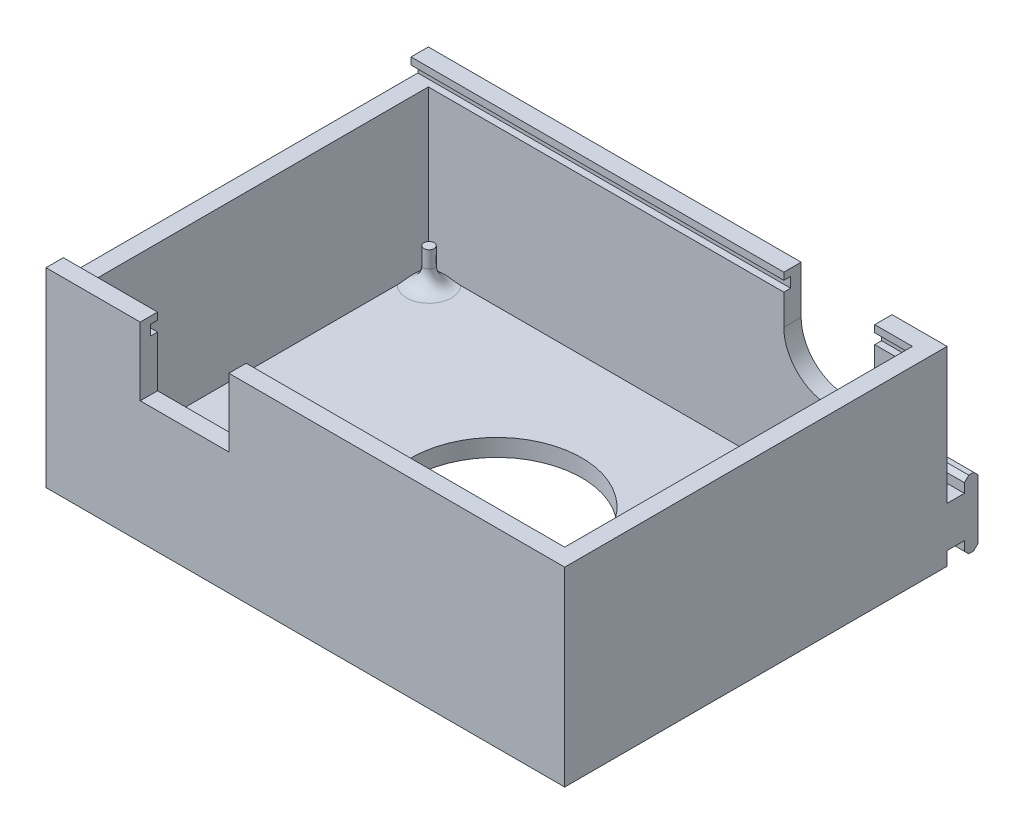
SolidWorks part; units mm, degrees
ref_plane "Front Plane" through (0, 0, 0) normal (0, 0, 1) x (1, 0, 0)
ref_plane "Top Plane" through (0, 0, 0) normal (0, 1, 0) x (1, 0, 0)
ref_plane "Right Plane" through (0, 0, 0) normal (1, 0, 0) x (0, 0, -1)
sketch "Sketch1" plane through (0, 0, 0) normal (0, 1, 0) x (1, 0, 0)
  line L0 (2.54, 2.54) -> (73.54, 2.54)
  line L1 (0, 0) -> (76.08, 0)
  line L2 (0, 0) -> (0, 56.08)
  line L3 (0, 56.08) -> (76.08, 56.08)
  line L4 (76.08, 0) -> (76.08, 56.08)
  line L5 (73.54, 2.54) -> (73.54, 53.54)
  line L6 (2.54, 53.54) -> (73.54, 53.54)
  line L7 (2.54, 2.54) -> (2.54, 53.54)
  dimension "D1" = 2.54
  dimension "D2" = 71
  dimension "D3" = 51
extrude "Boss-Extrude1" add sketch "Sketch1" along normal blind 25.4
sketch "Sketch2" plane through (0, 0, 0) normal (0, -1, 0) x (1, 0, 0)
  line L4 (0, 0) -> (0, -56.08)
  line L5 (0, -56.08) -> (76.08, -56.08)
  line L6 (76.08, -56.08) -> (76.08, 0)
  line L7 (76.08, 0) -> (0, 0)
  line L8 (0, 0) -> (0, -56.08)
  line L9 (0, -56.08) -> (76.08, -56.08)
  line L10 (76.08, -56.08) -> (76.08, 0)
  line L11 (76.08, 0) -> (0, 0)
  dimension "D1" = 0
extrude "Boss-Extrude2" add sketch "Sketch2" along normal blind 2.54
sketch "Sketch3" plane through (0, 0, -56.08) normal (0, 0, -1) x (-1, 0, 0)
  line L0 (-76.08, 25.4) -> (-76.08, -2.54) construction
  line L1 (-76.08, 25.4) -> (0, 25.4) construction
  line L2 (-68.0155, 18.4) -> (-68.0155, 25.4)
  line L3 (-54.6805, 18.4) -> (-54.6805, 25.4)
  line L4 (-54.6805, 25.4) -> (-68.0155, 25.4)
  arc A0 (-68.0155, 18.4) -> (-54.6805, 18.4) centre (-61.348, 18.4) ccw
  dimension "D3" = 13.335
  dimension "D1" = 14.732
  dimension "D2" = 7
extrude "Cut-Extrude1" cut sketch "Sketch3" against normal up to next
sketch "Sketch4" plane through (0, 0, 0) normal (-1, 0, 0) x (0, 0, 1)
  line L0 (-53.54, 25.4) -> (-53.54, 24.36)
  line L1 (-56.08, 25.4) -> (0, 25.4) construction
  line L2 (-53.54, 24.36) -> (-54.54, 24.36)
  line L3 (-54.54, 24.36) -> (-54.54, 22.86)
  line L4 (-54.54, 22.86) -> (-1.54, 22.86)
  line L5 (-1.54, 22.86) -> (-1.54, 24.36)
  line L6 (-1.54, 24.36) -> (-2.54, 24.36)
  line L7 (-2.54, 24.36) -> (-2.54, 25.4)
  line L8 (-2.54, 25.4) -> (-53.54, 25.4)
  line L9 (-2.54, 25.4) -> (-2.54, 0) construction
  line L10 (-53.54, 25.4) -> (-53.54, 0) construction
  dimension "D1" = 1
  dimension "D2" = 1.5
  dimension "D3" = 2.54
extrude "Cut-Extrude2" cut sketch "Sketch4" against normal up to surface (73.54 mm away) up to face at (73.54, 12.7, -28.04)
sketch "Sketch5" plane through (0, 0, 0) normal (0, 1, 0) x (1, 0, 0)
  line L1 (38.04, 51.29) -> (38.04, 53.54) construction
  line L2 (73.54, 53.54) -> (2.54, 53.54) construction
  line L4 (38.04, 4.79) -> (38.04, 2.54) construction
  line L5 (2.54, 2.54) -> (73.54, 2.54) construction
  line L6 (71.187, 28.04) -> (73.54, 28.04) construction
  line L7 (4.893, 51.29) -> (71.187, 51.29) construction
  line L8 (4.893, 51.29) -> (4.893, 4.79) construction
  line L9 (4.893, 4.79) -> (71.187, 4.79) construction
  line L10 (71.187, 51.29) -> (71.187, 4.79) construction
  line L11 (73.54, 2.54) -> (73.54, 53.54) construction
  line L14 (4.893, 28.04) -> (2.54, 28.04) construction
  line L15 (2.54, 53.54) -> (2.54, 2.54) construction
  circle A0 centre (4.893, 51.29) radius 0.75
  circle A1 centre (4.893, 4.79) radius 0.75
  circle A2 centre (71.187, 4.79) radius 0.75
  circle A3 centre (71.187, 51.29) radius 0.75
  dimension "D1" = 1.5
  dimension "D2" = 66.294
  dimension "D3" = 46.5
extrude "Boss-Extrude3" add sketch "Sketch5" along normal blind 5
fillet "Fillet1" radius 2.54 4 edges at (71.187, 0, -5.54) (4.893, 0, -5.54) (71.187, 0, -52.04) (4.893, 0, -52.04)
sketch "Sketch6" plane through (0, 0, 0) normal (0, 0, 1) x (1, 0, 0)
  line L0 (0, 25.4) -> (20.32, 25.4) construction
  line L1 (0, 25.4) -> (76.08, 25.4) construction
  line L3 (13.82, 25.4) -> (26.82, 25.4)
  line L4 (13.82, 25.4) -> (13.82, 15.4)
  line L5 (13.82, 15.4) -> (26.82, 15.4)
  line L6 (26.82, 25.4) -> (26.82, 15.4)
  point P9 (20.32, 25.4)
  dimension "D1" = 20.32
  dimension "D2" = 13
  dimension "D3" = 10
extrude "Cut-Extrude3" cut sketch "Sketch6" against normal up to next
sketch "Sketch7" plane through (0, 0, 0) normal (-1, 0, 0) x (0, 0, 1)
  line L0 (-56.08, -0.54) -> (-58.62, -0.54)
  line L1 (-56.08, 25.4) -> (-56.08, -2.54) construction
  line L2 (-58.62, -0.54) -> (-58.62, -2.54)
  line L3 (-58.62, -2.54) -> (-60.62, -2.54)
  line L4 (-60.62, -2.54) -> (-60.62, 7.46)
  line L5 (-60.62, 7.46) -> (-58.62, 7.46)
  line L6 (-58.62, 7.46) -> (-58.62, 5.46)
  line L7 (-58.62, 5.46) -> (-56.08, 5.46)
  line L8 (0, -2.54) -> (-56.08, -2.54) construction
  line L9 (-56.08, 5.46) -> (-56.08, -0.54)
  dimension "D1" = 10
  dimension "D2" = 2
  dimension "D3" = 2.54
  dimension "D4" = 2
extrude "Boss-Extrude4" add sketch "Sketch7" against normal up to surface (76.08 mm away) up to face at (76.08, 11.43, -28.04)
chamfer "Chamfer1" distance 0.635 angle 45 4 edges at (38.04, -2.54, -58.62) (38.04, -2.54, -60.62) (38.04, 7.46, -58.62) (38.04, 7.46, -60.62)
sketch "Sketch9" plane through (0, 0, 0) normal (0, 1, 0) x (1, 0, 0)
  line L0 (38.04, 53.54) -> (38.04, 2.54) construction
  line L1 (68.7867, 53.54) -> (7.2933, 53.54) construction
  line L2 (7.2933, 2.54) -> (68.7867, 2.54) construction
  circle A0 centre (38.04, 28.04) radius 12.5
  dimension "D1" = 25
extrude "Cut-Extrude4" cut sketch "Sketch9" against normal through all
equation "\"2.5vm\"=0.787402"
